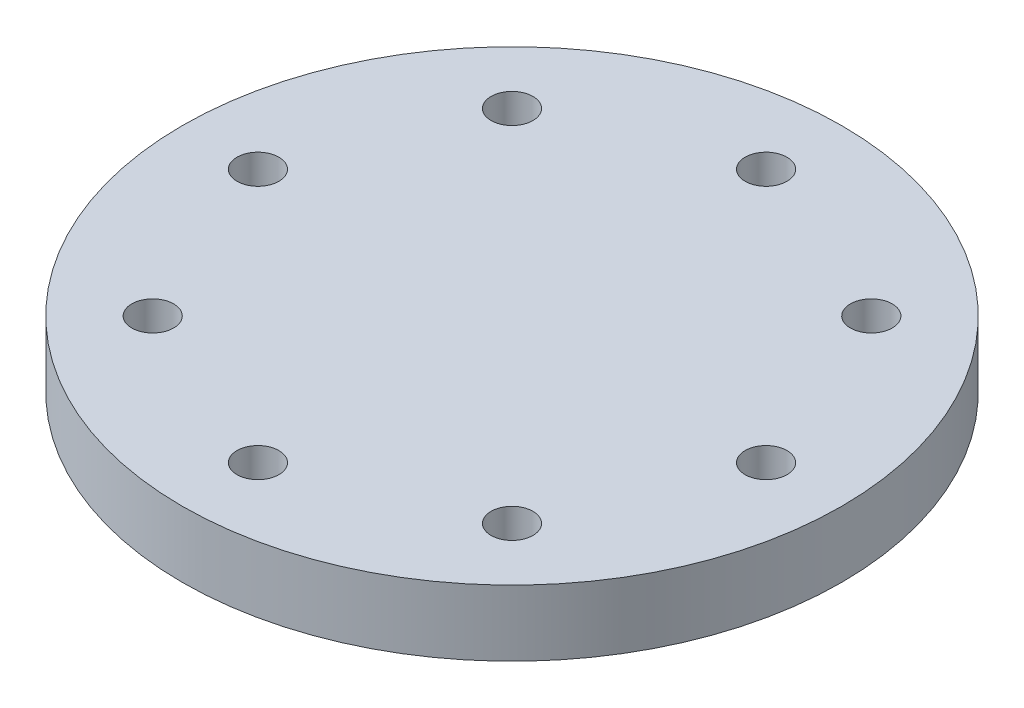
SolidWorks part; units mm, degrees
note: The reader was unsure of these and kept them because the rebuilt part matched: shared geometry of "草图1<8>", "草图1<9>", "草图1<10>".
ref_plane "前视基准面" through (0, 0, 0) normal (0, 0, 1) x (1, 0, 0)
ref_plane "上视基准面" through (0, 0, 0) normal (0, 1, 0) x (1, 0, 0)
ref_plane "右视基准面" through (0, 0, 0) normal (1, 0, 0) x (0, 0, -1)
sketch "草图1" plane through (0, 0, 0) normal (0, 1, 0) x (1, 0, 0)
  line L0 (0, -2) -> (7, -2)
  line L1 (0, 0) -> (7, 0)
  line L6 (0, 0) -> (0, -50)
  line L7 (0, -50) -> (0, 50)
  line L8 (0, -2) -> (0, 2)
  line L9 (0, 2) -> (7, 2)
  line L10 (7, -2) -> (7, 2)
  line L12 (0, 0) -> (-50, 0)
  line L13 (-50, 0) -> (50, 0)
  line L14 (0, 0) -> (0, -38.6052)
  line L16 (0, 50) -> (-50, 0)
  line L17 (0, 50) -> (50, 0)
  line L18 (-50, 0) -> (0, -50)
  line L19 (50, 0) -> (0, -50)
  line L20 (25, 25) -> (29.4901, 29.4901)
  circle A0 centre (0, 0) radius 50
  circle A9 centre (0, 0) radius 7
  circle A10 centre (0, 0) radius 11
  circle A11 centre (27.2451, 27.2451) radius 3.175
  circle A12 centre (38.5303, 0) radius 3.175
  circle A13 centre (27.2451, -27.2451) radius 3.175
  circle A14 centre (0, -38.5303) radius 3.175
  circle A15 centre (-27.2451, -27.2451) radius 3.175
  circle A16 centre (-38.5303, 0) radius 3.175
  circle A17 centre (-27.2451, 27.2451) radius 3.175
  circle A18 centre (0, 38.5303) radius 3.175
  point P26 (0, 0)
  point P36 (0, 0)
  dimension "D1" = 100
  dimension "D2" = 6.35
  dimension "D3" = 14
  dimension "D4" = 7
  dimension "D6" = 22
  dimension "D7" = 8
  dimension "D5" = 2
extrude "凸台-拉伸1" add sketch "草图1" along normal blind 10
extrude "凸台-拉伸2" add sketch "草图1<8>" against normal blind 25.5 contours L7 A10 L13 A9 | L13 A10 L14 A9 | L13 A10 L7 A9 L9 L10 | L14 A10 L13 L10 L0 A9
sketch "草图1<8>" plane through (0, 0, 0) normal (0, 1, 0) x (1, 0, 0) same geometry as "草图1"
sketch "草图4" plane through (0, 0, 0) normal (1, 0, 0) x (0, 0, -1)
  circle A0 centre (0, -8.2194) radius 3.175
  circle A1 centre (0, -20.5472) radius 3.175
  dimension "D1" = 6.35
  dimension "D2" = 6.35
sketch "草图2" plane through (0, 0, 0) normal (0, 0, 1) x (1, 0, 0)
  circle A0 centre (0, -6.8566) radius 3.175
  circle A1 centre (0, -19.3465) radius 3.175
  dimension "D1" = 6.35
  dimension "D2" = 6.35
extrude "切除-拉伸1" cut sketch "草图4" against normal blind 30
extrude "切除-拉伸2" cut sketch "草图2" against normal blind 30
extrude "凸台-拉伸3" add sketch "草图1<9>" along normal blind 10 contours L7 A9 L12 | L9 A9 L7 | L0 A9 L1 L6 | L1 A9 L9 L7 | L6 A9 L0 | L12 A9 L6 | A9 L0 L10 | A9 L10 L9
sketch "草图1<9>" plane through (0, 0, 0) normal (0, 1, 0) x (1, 0, 0) same geometry as "草图1"
extrude "凸台-拉伸4" add sketch "草图1<10>" along normal blind 10 contours L1 A9 L9 L7 | L0 A9 L1 L6 | A9 L0 L10 | A9 L10 L9
sketch "草图1<10>" plane through (0, 0, 0) normal (0, 1, 0) x (1, 0, 0) same geometry as "草图1"
sketch "Sketch1" plane through (0, -25.5, 0) normal (0, -1, 0) x (1, 0, 0)
  line L0 (-11, 0) -> (11, 0) construction
  line L1 (0, 11) -> (0, -11) construction
  circle A0 centre (0, 0) radius 11 construction
  circle A1 centre (0, 0) radius 11 construction
  point P9 (0, 0)
